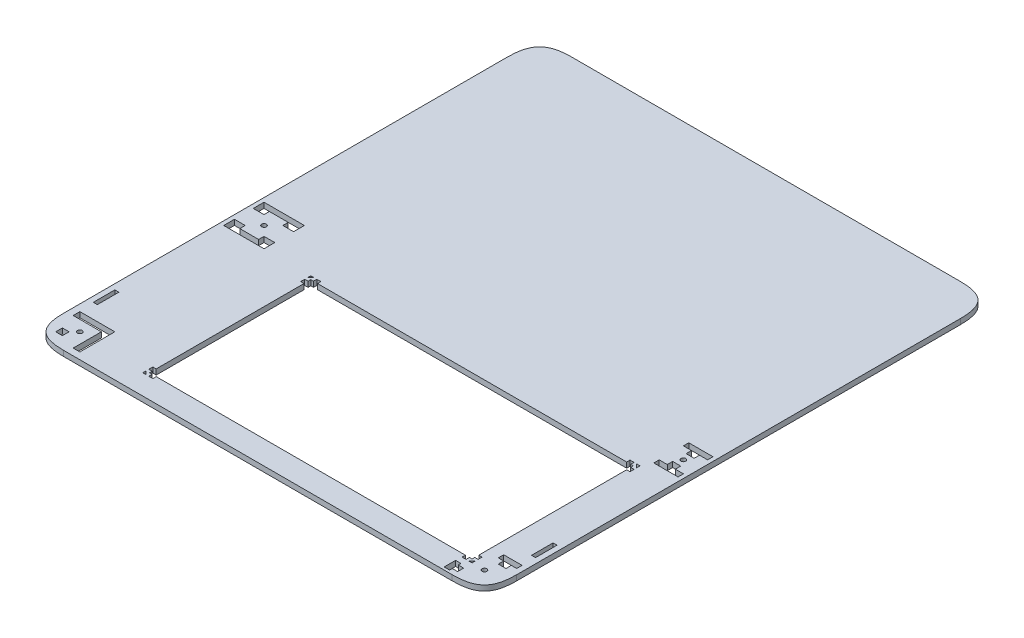
SolidWorks part; units mm, degrees
ref_plane "Front Plane" through (0, 0, 0) normal (0, 0, 1) x (1, 0, 0)
ref_plane "Top Plane" through (0, 0, 0) normal (0, 1, 0) x (1, 0, 0)
ref_plane "Right Plane" through (0, 0, 0) normal (1, 0, 0) x (0, 0, -1)
sketch "Sketch1" plane through (0, 0, 0) normal (0, 1, 0) x (1, 0, 0)
  line L1 (0, 0) -> (337, 0)
  line L2 (0, 0) -> (0, 377.97)
  line L3 (0, 377.97) -> (337, 377.97)
  line L4 (337, 0) -> (337, 377.97)
  line L5 (70.28, 137.5) -> (310.28, 137.5)
  line L6 (70.28, 137.5) -> (70.28, 17.5)
  line L7 (70.28, 17.5) -> (310.28, 17.5)
  line L8 (310.28, 137.5) -> (310.28, 17.5)
  dimension "D1" = 337
  dimension "D2" = 377.97
  dimension "D3" = 240
  dimension "D4" = 120
  dimension "D5" = 17.5
  dimension "D6" = 26.72
extrude "Boss-Extrude1" add sketch "Sketch1" against normal blind 4
fillet "Fillet1" radius 24 4 edges at (0, -2, 0) (337, -2, 0) (0, -2, -377.97) (337, -2, -377.97) conic rho 0.55
sketch "Sketch3" plane through (0, 0, 0) normal (0, 1, 0) x (1, 0, 0)
  line L0 (337, 24) -> (337, 353.97) construction
  line L1 (24, 0) -> (313, 0) construction
  line L2 (0, 353.97) -> (0, 24) construction
  line L3 (309, 4) -> (309, 2)
  line L4 (305, 10.5) -> (309, 10.5)
  line L5 (305, 10.5) -> (305, 2)
  line L6 (305, 2) -> (309, 2)
  line L7 (309, 10.5) -> (309, 8.5)
  line L8 (309, 8.5) -> (313, 8.5)
  line L10 (309, 4) -> (313, 4)
  line L11 (313, 8.5) -> (313, 4)
  line L12 (329, 28) -> (333, 28)
  line L13 (319.28, 32) -> (333, 32)
  line L14 (319.28, 32) -> (319.28, 28)
  line L15 (319.28, 28) -> (323.28, 28)
  line L16 (333, 32) -> (333, 28)
  line L18 (323.28, 28) -> (323.28, 24)
  line L19 (323.28, 24) -> (329, 24)
  line L20 (329, 28) -> (329, 24)
  line L21 (328, 151) -> (334, 151)
  line L30 (26, 5) -> (31, 5)
  line L36 (26, 5) -> (26, 26)
  line L37 (9, 14) -> (14, 14)
  line L38 (9, 14) -> (9, 9)
  line L39 (9, 9) -> (14, 9)
  line L40 (14, 14) -> (14, 9)
  line L41 (26, 31) -> (31, 31)
  line L42 (31, 5) -> (31, 31)
  line L43 (26, 31) -> (5, 31)
  line L45 (26, 26) -> (5, 26)
  line L46 (5, 31) -> (5, 26)
  line L47 (3, 140) -> (33, 140)
  line L48 (3, 140) -> (3, 144)
  line L49 (11, 144) -> (25, 144)
  line L50 (33, 140) -> (33, 144)
  line L52 (3, 144) -> (3, 148)
  line L53 (3, 148) -> (11, 148)
  line L54 (11, 144) -> (11, 148)
  line L56 (33, 144) -> (33, 148)
  line L57 (33, 148) -> (25, 148)
  line L58 (25, 144) -> (25, 148)
  line L59 (3, 170) -> (33, 170)
  line L60 (3, 170) -> (3, 166)
  line L61 (11, 166) -> (25, 166)
  line L62 (33, 170) -> (33, 166)
  line L64 (3, 166) -> (3, 162)
  line L65 (3, 162) -> (11, 162)
  line L66 (11, 166) -> (11, 162)
  line L68 (33, 166) -> (33, 162)
  line L69 (33, 162) -> (25, 162)
  line L70 (25, 166) -> (25, 162)
  line L71 (316, 147) -> (334, 147)
  line L72 (316, 147) -> (316, 151)
  line L73 (316, 151) -> (322, 151)
  line L74 (334, 147) -> (334, 151)
  line L76 (322, 151) -> (322, 155)
  line L77 (322, 155) -> (328, 155)
  line L78 (328, 151) -> (328, 155)
  line L79 (328, 169) -> (334, 169)
  line L80 (316, 173) -> (334, 173)
  line L81 (316, 173) -> (316, 169)
  line L82 (316, 169) -> (322, 169)
  line L83 (334, 173) -> (334, 169)
  line L85 (322, 169) -> (322, 165)
  line L86 (322, 165) -> (328, 165)
  line L87 (328, 169) -> (328, 165)
  line L89 (333, 42) -> (330, 42)
  line L90 (333, 42) -> (333, 58)
  line L91 (333, 58) -> (330, 58)
  line L92 (330, 42) -> (330, 58)
  line L93 (4, 42) -> (7, 42)
  line L94 (4, 42) -> (4, 58)
  line L95 (4, 58) -> (7, 58)
  line L96 (7, 42) -> (7, 58)
  circle A0 centre (322, 15) radius 1.75
  circle A1 centre (18, 18) radius 1.75
  circle A2 centre (18, 155) radius 1.75
  circle A3 centre (325, 160) radius 1.75
  point P37 (5, 28.5)
  dimension "D3" = 3.5
  dimension "D6" = 3.5
  dimension "D45" = 3.5
  dimension "D62" = 3.5
  dimension "D1" = 15
  dimension "D2" = 15
  dimension "D4" = 18
  dimension "D5" = 18
  dimension "D7" = 24
  dimension "D8" = 4
  dimension "D9" = 2
  dimension "D10" = 2
  dimension "D11" = 4.5
  dimension "D12" = 2
  dimension "D13" = 4
  dimension "D14" = 4
  dimension "D15" = 13.72
  dimension "D16" = 4
  dimension "D17" = 4
  dimension "D18" = 4
  dimension "D19" = 4
  dimension "D20" = 24
  dimension "D21" = 5
  dimension "D22" = 5
  dimension "D23" = 9
  dimension "D24" = 9
  dimension "D25" = 26
  dimension "D26" = 5
  dimension "D27" = 5
  dimension "D28" = 5
  dimension "D29" = 21
  dimension "D30" = 5
  dimension "D31" = 30
  dimension "D32" = 4
  dimension "D33" = 4
  dimension "D34" = 8
  dimension "D35" = 8
  dimension "D36" = 4
  dimension "D37" = 30
  dimension "D38" = 4
  dimension "D39" = 4
  dimension "D40" = 4
  dimension "D41" = 30
  dimension "D42" = 140
  dimension "D43" = 3
  dimension "D44" = 3
  dimension "D46" = 11
  dimension "D47" = 4
  dimension "D48" = 4
  dimension "D49" = 4
  dimension "D50" = 18
  dimension "D51" = 3
  dimension "D52" = 6
  dimension "D53" = 6
  dimension "D54" = 4
  dimension "D55" = 4
  dimension "D56" = 4
  dimension "D57" = 18
  dimension "D58" = 6
  dimension "D59" = 6
  dimension "D60" = 10
  dimension "D61" = 147
  dimension "D63" = 5
  dimension "D64" = 9
  dimension "D65" = 3
  dimension "D66" = 16
  dimension "D67" = 10
  dimension "D68" = 4
  dimension "D69" = 4
  dimension "D70" = 16
  dimension "D71" = 3
  dimension "D72" = 0
extrude "Cut-Extrude1" cut sketch "Sketch3" against normal up to next
ref_plane "Plane3" through (190.28, 0, 0) normal (-1, 0, 0) x (0, 0, 1)
ref_plane "Plane6" through (0, 0, -77.5) normal (0, 0, 1) x (1, 0, 0)
sketch "Sketch5" plane through (0, 0, 0) normal (0, 1, 0) x (1, 0, 0)
  line L0 (310.28, 17.5) -> (310.28, 137.5) construction
  line L3 (310.28, 15) -> (312.78, 15)
  line L4 (312.78, 17.5) -> (312.78, 15)
  line L5 (310.28, 22.5) -> (312.78, 22.5)
  line L6 (310.28, 22.5) -> (310.28, 19.5)
  line L7 (310.28, 19.5) -> (312.78, 19.5)
  line L8 (312.78, 22.5) -> (312.78, 19.5)
  line L9 (70.28, 17.5) -> (310.28, 17.5) construction
  line L10 (305.28, 17.5) -> (308.28, 17.5)
  line L11 (305.28, 17.5) -> (305.28, 15)
  line L12 (305.28, 15) -> (308.28, 15)
  line L13 (308.28, 17.5) -> (308.28, 15)
  line L14 (310.28, 15) -> (312.78, 17.5)
  dimension "D1" = 2.5
  dimension "D2" = 2.5
  dimension "D4" = 3
  dimension "D6" = 3
extrude "Cut-Extrude2" cut sketch "Sketch5" against normal up to next
mirror "Mirror1" about plane through (0, 0, -77.5) normal (0, 0, 1) of "Cut-Extrude2" second plane through (190.28, 0, 0) second plane normal (-1, 0, 0)
